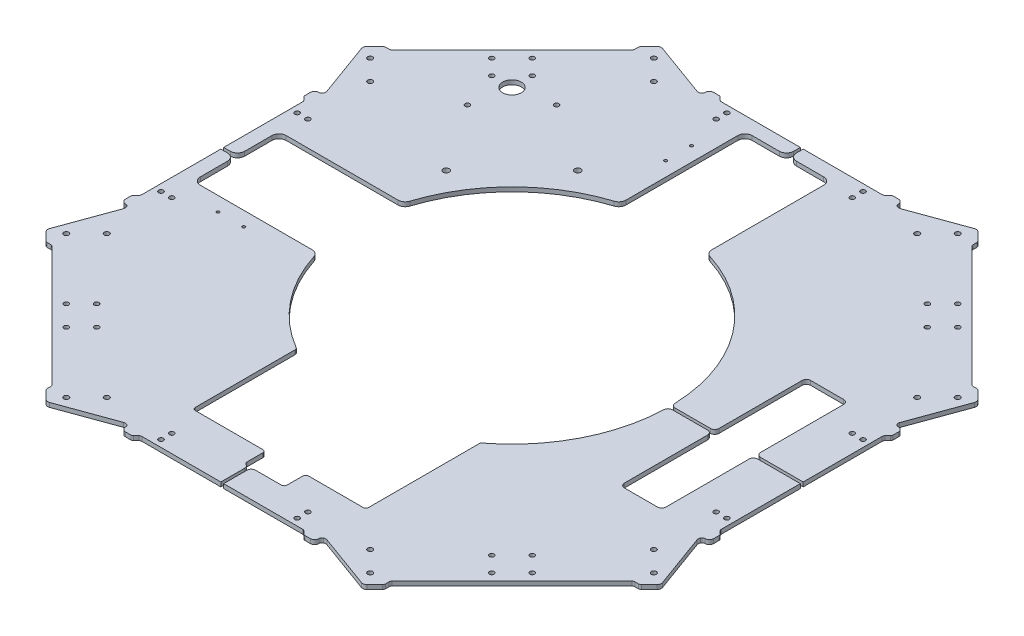
SolidWorks part; units mm, degrees
material "POM 乙缩醛共聚物"
ref_plane "前视基准面" through (0, 0, 0) normal (0, 0, 1) x (1, 0, 0)
ref_plane "上视基准面" through (0, 0, 0) normal (0, 1, 0) x (1, 0, 0)
ref_plane "右视基准面" through (0, 0, 0) normal (1, 0, 0) x (0, 0, -1)
sketch "草图1" plane through (0, 0, 0) normal (0, 1, 0) x (1, 0, 0)
  line L0 (-213.25, 0) -> (213.25, 0) construction
  line L1 (213.25, -47.5) -> (213.25, 47.5) construction
  line L2 (0, -213.25) -> (0, 213.25) construction
  line L3 (-213.25, -47.5) -> (-213.25, 47.5) construction
  line L4 (213.25, 0) -> (221.25, 0) construction
  line L5 (221.25, -67.5) -> (221.25, 67.5)
  line L6 (221.25, 67.5) -> (201.2006, 67.5)
  line L7 (0, 0) -> (180.3122, 180.3122) construction
  line L8 (201.2006, 67.5) -> (67.5, 201.2006)
  line L9 (67.5, 221.25) -> (67.5, 201.2006)
  line L10 (-67.5, 221.25) -> (67.5, 221.25)
  line L11 (-67.5, 221.25) -> (-67.5, 201.2006)
  line L12 (-201.2006, 67.5) -> (-67.5, 201.2006)
  line L13 (-221.25, 67.5) -> (-201.2006, 67.5)
  line L14 (-221.25, -67.5) -> (-221.25, 67.5)
  line L15 (221.25, -67.5) -> (201.2006, -67.5)
  line L16 (201.2006, -67.5) -> (67.5, -201.2006)
  line L17 (67.5, -221.25) -> (67.5, -201.2006)
  line L18 (-221.25, -67.5) -> (-201.2006, -67.5)
  line L19 (-201.2006, -67.5) -> (-67.5, -201.2006)
  line L20 (-67.5, -221.25) -> (-67.5, -201.2006)
  line L21 (-67.5, -221.25) -> (67.5, -221.25)
  circle A0 centre (0, 0) radius 100 construction
  circle A2 centre (0, 0) radius 110
  point P19 (134.3503, 134.3503)
  point P22 (0, 221.25)
  point P31 (-221.25, 0)
  dimension "D1" = 200
  dimension "D4" = 213.25
  dimension "D2" = 213.25
  dimension "D3" = 47.5
  dimension "D5" = 8
  dimension "D6" = 67.5
  dimension "D7" = 10
  dimension "D8" = 255
  dimension "D9" = 65
extrude "凸台-拉伸1" add sketch "草图1" along normal blind 3
sketch "草图2" plane through (0, 3, 0) normal (0, 1, 0) x (1, 0, 0)
  line L0 (0, 0) -> (0, -168) construction
  line L2 (-55, -70) -> (55, -70)
  line L3 (-55, -70) -> (-55, -168)
  line L4 (-55, -168) -> (55, -168)
  line L5 (55, -70) -> (55, -168)
  line L6 (-55, -70) -> (55, -168) construction
  line L7 (-55, -168) -> (55, -70) construction
  point P3 (0, -119)
  dimension "D1" = 168
  dimension "D2" = 110
  dimension "D3" = 98
extrude "切除-拉伸1" cut sketch "草图2" against normal blind 10
sketch "草图3" plane through (0, 3, 0) normal (0, 1, 0) x (1, 0, 0)
  line L0 (55, -168) -> (66, -168)
  line L1 (66, -168) -> (66, -78)
  line L2 (66, -78) -> (55, -78)
  line L3 (55, -78) -> (55, -168)
  dimension "D1" = 11
  dimension "D2" = 90
extrude "切除-拉伸2" cut sketch "草图3" against normal blind 10
sketch "草图4" plane through (0, 3, 0) normal (0, 1, 0) x (1, 0, 0)
  line L0 (-55, -168) -> (66, -168) construction
  line L1 (-4, -153) -> (24, -153)
  line L2 (-4, -153) -> (-4, -183)
  line L3 (-4, -183) -> (24, -183)
  line L4 (24, -153) -> (24, -183)
  line L5 (-4, -153) -> (24, -183) construction
  line L6 (-4, -183) -> (24, -153) construction
  line L7 (0, 0) -> (0, -232.4473) construction
  point P0 (10, -168)
  dimension "D1" = 10
  dimension "D2" = 28
  dimension "D3" = 30
extrude "切除-拉伸3" cut sketch "草图4" against normal blind 10
fillet "圆角1" radius 2 24 edges at (-4, 1.5, 183) (-4, 1.5, 168) (-55, 1.5, 168) (-55, 1.5, 95.2628) (66, 1.5, 88) (66, 1.5, 168) (24, 1.5, 183) (201.2006, 1.5, -67.5) (67.5, 1.5, -201.2006) (67.5, 1.5, -221.25) (-67.5, 1.5, -221.25) (-67.5, 1.5, -201.2006) (-201.2006, 1.5, -67.5) (-221.25, 1.5, -67.5) (-221.25, 1.5, 67.5) (-201.2006, 1.5, 67.5) (-67.5, 1.5, 201.2006) (-67.5, 1.5, 221.25) (67.5, 1.5, 221.25) (67.5, 1.5, 201.2006) (201.2006, 1.5, 67.5) (221.25, 1.5, 67.5) (221.25, 1.5, -67.5) (24, 1.5, 168)
sketch "草图5" plane through (0, 3, 0) normal (0, 1, 0) x (1, 0, 0)
  line L0 (0, 0) -> (-208.25, 0) construction
  line L1 (-208.25, -47.5) -> (-208.25, 47.5) construction
  line L2 (-208.25, 47.5) -> (-197.5, 47.5) construction
  line L3 (-197.5, 47.5) -> (-190, 47.5) construction
  line L4 (-197.5, -47.5) -> (-190, -47.5) construction
  line L5 (-208.25, -47.5) -> (-197.5, -47.5) construction
  line L6 (-47.5, 208.25) -> (47.5, 208.25) construction
  line L7 (0, 208.25) -> (0, 0) construction
  circle A0 centre (-208.25, 47.5) radius 2.65
  circle A1 centre (-197.5, 47.5) radius 1.65
  circle A2 centre (-190, 47.5) radius 1.65
  circle A3 centre (-190, -47.5) radius 1.65
  circle A4 centre (-197.5, -47.5) radius 1.65
  circle A5 centre (-208.25, -47.5) radius 2.65
  circle A24 centre (47.5, 190) radius 1.65
  circle A25 centre (47.5, 197.5) radius 1.65
  circle A26 centre (47.5, 208.25) radius 2.65
  circle A27 centre (-47.5, 208.25) radius 2.65
  circle A28 centre (-47.5, 197.5) radius 1.65
  circle A29 centre (-47.5, 190) radius 1.65
  circle A30 centre (190, -47.5) radius 1.65
  circle A31 centre (197.5, -47.5) radius 1.65
  circle A32 centre (208.25, -47.5) radius 2.65
  circle A33 centre (208.25, 47.5) radius 2.65
  circle A34 centre (197.5, 47.5) radius 1.65
  circle A35 centre (190, 47.5) radius 1.65
  circle A36 centre (-47.5, -190) radius 1.65
  circle A37 centre (-47.5, -197.5) radius 1.65
  circle A38 centre (-47.5, -208.25) radius 2.65
  circle A39 centre (47.5, -208.25) radius 2.65
  circle A40 centre (47.5, -197.5) radius 1.65
  circle A41 centre (47.5, -190) radius 1.65
  point P55 (1.5152, 1.5152)
  dimension "D2" = 5.3
  dimension "D4" = 7.5
  dimension "D5" = 3.3
  dimension "D7" = 95
  dimension "D1" = 208.25
  dimension "D3" = 10.75
  dimension "D6" = 4
extrude "切除-拉伸4" cut sketch "草图5" against normal blind 10
sketch "草图6" plane through (0, 3, 0) normal (0, 1, 0) x (1, 0, 0)
  line L0 (0, 0) -> (0, -221.25) construction
  line L1 (-65.5, -221.25) -> (65.5, -221.25) construction
  line L2 (67.5, -219.25) -> (67.5, -202.029) construction
  line L3 (-67.5, -237.25) -> (67.5, -237.25)
  line L4 (-67.5, -237.25) -> (-67.5, -205.25)
  line L5 (-67.5, -205.25) -> (67.5, -205.25)
  line L6 (67.5, -237.25) -> (67.5, -205.25)
  line L7 (-67.5, -237.25) -> (67.5, -205.25) construction
  line L8 (-67.5, -205.25) -> (67.5, -237.25) construction
  line L9 (-237.25, 67.5) -> (-237.25, -67.5)
  line L10 (-237.25, 67.5) -> (-205.25, 67.5)
  line L11 (-237.25, -67.5) -> (-205.25, -67.5)
  line L12 (-205.25, 67.5) -> (-205.25, -67.5)
  line L21 (-237.25, 67.5) -> (-205.25, -67.5) construction
  line L23 (67.5, 237.25) -> (-67.5, 237.25) [skipped]
  line L24 (67.5, 237.25) -> (67.5, 205.25) [skipped]
  line L25 (-67.5, 237.25) -> (-67.5, 205.25) [skipped]
  line L26 (67.5, 205.25) -> (-67.5, 205.25) [skipped]
  line L27 (237.25, -67.5) -> (237.25, 67.5) [skipped]
  line L28 (237.25, -67.5) -> (205.25, -67.5) [skipped]
  line L29 (237.25, 67.5) -> (205.25, 67.5) [skipped]
  line L30 (205.25, -67.5) -> (205.25, 67.5) [skipped]
  line L34 (237.25, 67.5) -> (205.25, 67.5)
  line L35 (205.25, 67.5) -> (205.25, -67.5)
  line L36 (237.25, -67.5) -> (205.25, -67.5)
  line L37 (237.25, 67.5) -> (237.25, -67.5)
  line L38 (-221.25, 0) -> (0, 0) construction
  line L39 (-219.5626, -92.2876) -> (-219.5626, -92.9346) construction
  line L40 (-67.5, 205.25) -> (67.5, 205.25)
  line L41 (-205.25, 67.5) -> (-237.25, -67.5) construction
  line L42 (67.5, 237.25) -> (67.5, 205.25)
  line L43 (-67.5, 237.25) -> (67.5, 237.25)
  line L44 (-67.5, 237.25) -> (-67.5, 205.25)
  point P26 (0, 0)
  dimension "D1" = 16
  dimension "D2" = 4
extrude "切除-拉伸5" cut sketch "草图6" against normal through all
sketch "草图7" plane through (0, 3, 0) normal (0, 1, 0) x (1, 0, 0)
  line L0 (0, 0) -> (169.5, 0) construction
  line L3 (140.5, 65) -> (169.5, 65)
  line L4 (140.5, 65) -> (140.5, -65)
  line L5 (140.5, -65) -> (169.5, -65)
  line L6 (169.5, 65) -> (169.5, -65)
  line L7 (140.5, 65) -> (169.5, -65) construction
  line L8 (140.5, -65) -> (169.5, 65) construction
  point P5 (155, 0)
  dimension "D1" = 130
  dimension "D2" = 29
  dimension "D3" = 155
extrude "切除-拉伸6" cut sketch "草图7" against normal blind 10
sketch "草图8" plane through (0, 3, 0) normal (0, 1, 0) x (1, 0, 0)
  line L0 (0, 0) -> (134.3503, -134.3503) construction
  line L1 (68.0858, -200.6148) -> (200.6148, -68.0858) construction
  line L2 (134.3503, -134.3503) -> (162.6346, -162.6346) construction
  line L3 (110.6622, -214.6069) -> (214.6069, -110.6622)
  line L4 (214.6069, -110.6622) -> (199.5118, -69.1888)
  line L5 (110.6622, -214.6069) -> (69.1888, -199.5118)
  line L6 (199.5118, -69.1888) -> (69.1888, -199.5118)
  line L7 (0, 0) -> (252.2182, 0) construction
  line L8 (0, 0) -> (0, -92.3729) construction
  line L9 (214.6069, 110.6622) -> (199.5118, 69.1888)
  line L10 (110.6622, 214.6069) -> (214.6069, 110.6622)
  line L11 (110.6622, 214.6069) -> (69.1888, 199.5118)
  line L12 (199.5118, 69.1888) -> (69.1888, 199.5118)
  line L13 (-214.6069, -110.6622) -> (-199.5118, -69.1888)
  line L14 (-110.6622, -214.6069) -> (-214.6069, -110.6622)
  line L15 (-110.6622, -214.6069) -> (-69.1888, -199.5118)
  line L16 (-199.5118, -69.1888) -> (-69.1888, -199.5118)
  line L17 (-110.6622, 214.6069) -> (-214.6069, 110.6622)
  line L18 (-110.6622, 214.6069) -> (-69.1888, 199.5118)
  line L19 (-199.5118, 69.1888) -> (-69.1888, 199.5118)
  line L20 (-214.6069, 110.6622) -> (-199.5118, 69.1888)
  dimension "D1" = 40
  dimension "D2" = 73.5
  dimension "D3" = 115
extrude "凸台-拉伸2" add sketch "草图8" against normal up to surface (3 mm away) up to face at (155, 0, 0)
ref_plane "基准面1" through (0, 0, 0) normal (-0.7071, 0, 0.7071) x (0.7071, 0, 0.7071)
sketch "草图12" plane through (0, 3, 0) normal (0, 1, 0) x (1, 0, 0)
  line L0 (0, 0) -> (162.6346, -162.6346) construction
  line L1 (110.6622, -214.6069) -> (214.6069, -110.6622) construction
  line L2 (155.5635, -155.5635) -> (162.6346, -148.4924) construction
  line L3 (162.6346, -148.4924) -> (152.028, -137.8858) construction
  line L4 (0, 0) -> (24.1105, 24.1105) construction
  line L5 (0, 0) -> (252.2182, 0) construction
  line L6 (162.6346, 148.4924) -> (152.028, 137.8858) construction
  line L7 (252.2182, -23.8295) -> (253.2892, -23.8295) construction
  line L8 (0, 0) -> (0, 85.4115) construction
  line L9 (155.5635, 155.5635) -> (162.6346, 148.4924) construction
  line L10 (-162.6346, -148.4924) -> (-152.028, -137.8858) construction
  line L11 (-155.5635, -155.5635) -> (-162.6346, -148.4924) construction
  line L12 (0, 0) -> (-162.6346, -162.6346) construction
  line L13 (-155.5635, 155.5635) -> (-162.6346, 148.4924) construction
  line L14 (-162.6346, 148.4924) -> (-152.028, 137.8858) construction
  circle A0 centre (162.6346, -148.4924) radius 1.65
  circle A1 centre (152.028, -137.8858) radius 1.65
  circle A2 centre (137.8858, -152.028) radius 1.65
  circle A3 centre (148.4924, -162.6346) radius 1.65
  circle A4 centre (148.4924, 162.6346) radius 1.65
  circle A5 centre (137.8858, 152.028) radius 1.65
  circle A6 centre (152.028, 137.8858) radius 1.65
  circle A7 centre (162.6346, 148.4924) radius 1.65
  circle A8 centre (-148.4924, -162.6346) radius 1.65
  circle A9 centre (-137.8858, -152.028) radius 1.65
  circle A10 centre (-152.028, -137.8858) radius 1.65
  circle A11 centre (-162.6346, -148.4924) radius 1.65
  circle A12 centre (-162.6346, 148.4924) radius 1.65
  circle A13 centre (-152.028, 137.8858) radius 1.65
  circle A14 centre (-137.8858, 152.028) radius 1.65
  circle A15 centre (-148.4924, 162.6346) radius 1.65
  dimension "D1" = 3.3
  dimension "D2" = 3.3
  dimension "D3" = 15
  dimension "D4" = 20
  dimension "D5" = 205
extrude "切除-拉伸7" cut sketch "草图12" against normal blind 112
sketch "草图13" plane through (0, 3, 0) normal (0, 1, 0) x (1, 0, 0)
  line L0 (-205.25, 0) -> (205.25, 0)
  line L1 (-205.25, -67.5) -> (-205.25, 67.5) construction
  line L2 (205.25, 67.5) -> (205.25, -67.5) construction
extrude "切除-拉伸-薄壁1" cut sketch "草图13" against normal through all both and the other way through all thin thin type mid plane wall 2
sketch "草图14" plane through (0, 3, 0) normal (0, 1, 0) x (1, 0, 0)
  line L0 (0, 205.25) -> (0, -205.25)
  line L1 (-67.5, 205.25) -> (67.5, 205.25) construction
  line L2 (67.5, -205.25) -> (-67.5, -205.25) construction
extrude "切除-拉伸-薄壁2" cut sketch "草图14" against normal through all and the other way through all thin thin type mid plane wall 2
fillet "圆角2" radius 3 8 edges at (-1, 1.5, 205.25) (-69.1888, 1.5, 199.5118) (-67.5, 1.5, 205.25) (-205.25, 1.5, 1) (-199.5118, 1.5, 69.1888) (-205.25, 1.5, 67.5) (-214.6069, 1.5, 110.6622) (-110.6622, 1.5, 214.6069)
fillet "圆角3" radius 3 14 edges at (169.5, 1.5, 65) (140.5, 1.5, 65) (109.9955, 1.5, 1) (140.5, 1.5, 1) (169.5, 1.5, 1) (205.25, 1.5, 1) (205.25, 1.5, 67.5) (199.5118, 1.5, 69.1888) (214.6069, 1.5, 110.6622) (110.6622, 1.5, 214.6069) (69.1888, 1.5, 199.5118) (67.5, 1.5, 205.25) (1, 1.5, 183) (1, 1.5, 205.25)
fillet "圆角4" radius 3 13 edges at (1, 1.5, -109.9955) (1, 1.5, -205.25) (69.1888, 1.5, -199.5118) (67.5, 1.5, -205.25) (110.6622, 1.5, -214.6069) (214.6069, 1.5, -110.6622) (205.25, 1.5, -67.5) (169.5, 1.5, -65) (140.5, 1.5, -65) (109.9955, 1.5, -1) (140.5, 1.5, -1) (169.5, 1.5, -1) (205.25, 1.5, -1)
fillet "圆角5" radius 3 10 edges at (-67.5, 1.5, -205.25) (-69.1888, 1.5, -199.5118) (-110.6622, 1.5, -214.6069) (-214.6069, 1.5, -110.6622) (-199.5118, 1.5, -69.1888) (-205.25, 1.5, -67.5) (-205.25, 1.5, -1) (-109.9955, 1.5, -1) (-1, 1.5, -109.9955) (-1, 1.5, -205.25)
fillet "圆角6" radius 3 2 edges at (-1, 1.5, 183) (-109.9955, 1.5, 1)
sketch "草图15" plane through (0, 0, 0) normal (0, -1, 0) x (1, 0, 0)
  line L0 (148.4924, -162.6346) -> (106.066, -205.061) construction
  line L1 (162.6346, -162.6346) -> (105.0927, -105.0927) construction
  line L2 (112.0136, -213.2555) -> (213.2555, -112.0136) construction
  line L3 (162.6346, -162.6346) -> (213.2555, -112.0136) construction
  line L4 (106.066, -205.061) -> (91.9239, -190.9188) construction
  line L5 (205.061, -106.066) -> (190.9188, -91.9239) construction
  line L6 (162.6346, -148.4924) -> (205.061, -106.066) construction
  line L7 (0, 0) -> (248.6294, 0) construction
  line L8 (0, 0) -> (0, -244.0653) construction
  line L9 (-162.6346, -148.4924) -> (-205.061, -106.066) construction
  line L10 (-205.061, -106.066) -> (-190.9188, -91.9239) construction
  line L11 (-106.066, -205.061) -> (-91.9239, -190.9188) construction
  line L12 (-162.6346, -162.6346) -> (-213.2555, -112.0136) construction
  line L13 (-162.6346, -162.6346) -> (-105.0927, -105.0927) construction
  line L14 (-148.4924, -162.6346) -> (-106.066, -205.061) construction
  line L15 (-148.4924, 162.6346) -> (-106.066, 205.061) construction
  line L16 (-162.6346, 162.6346) -> (-105.0927, 105.0927) construction
  line L17 (-162.6346, 162.6346) -> (-213.2555, 112.0136) construction
  line L18 (-106.066, 205.061) -> (-91.9239, 190.9188) construction
  line L19 (-205.061, 106.066) -> (-190.9188, 91.9239) construction
  line L20 (-162.6346, 148.4924) -> (-205.061, 106.066) construction
  line L21 (162.6346, 148.4924) -> (205.061, 106.066) construction
  line L22 (205.061, 106.066) -> (190.9188, 91.9239) construction
  line L23 (106.066, 205.061) -> (91.9239, 190.9188) construction
  line L24 (162.6346, 162.6346) -> (213.2555, 112.0136) construction
  line L25 (162.6346, 162.6346) -> (105.0927, 105.0927) construction
  line L26 (148.4924, 162.6346) -> (106.066, 205.061) construction
  circle A0 centre (106.066, -205.061) radius 1.75
  circle A1 centre (91.9239, -190.9188) radius 1.75
  circle A2 centre (190.9188, -91.9239) radius 1.75
  circle A3 centre (205.061, -106.066) radius 1.75
  circle A4 centre (-205.061, -106.066) radius 1.75
  circle A5 centre (-190.9188, -91.9239) radius 1.75
  circle A6 centre (-91.9239, -190.9188) radius 1.75
  circle A7 centre (-106.066, -205.061) radius 1.75
  circle A8 centre (-106.066, 205.061) radius 1.75
  circle A9 centre (-91.9239, 190.9188) radius 1.75
  circle A10 centre (-190.9188, 91.9239) radius 1.75
  circle A11 centre (-205.061, 106.066) radius 1.75
  circle A12 centre (205.061, 106.066) radius 1.75
  circle A13 centre (190.9188, 91.9239) radius 1.75
  circle A14 centre (91.9239, 190.9188) radius 1.75
  circle A15 centre (106.066, 205.061) radius 1.75
  dimension "D2" = 3.5
  dimension "D4" = 3.5
  dimension "D1" = 140
  dimension "D3" = 20
extrude "切除-拉伸8" cut sketch "草图15" against normal blind 10
sketch "草图16" plane through (0, 3, 0) normal (0, 1, 0) x (1, 0, 0)
  line L0 (0, 0) -> (-162.6346, 162.6346) construction
  line L1 (-112.0136, 213.2555) -> (-213.2555, 112.0136) construction
  line L2 (-127.2792, 127.2792) -> (-111.7229, 142.8356) construction
  line L3 (-87.6812, 87.6812) -> (-64.7003, 110.6622) construction
  circle A0 centre (-111.7229, 142.8356) radius 1.65
  circle A1 centre (-64.7003, 110.6622) radius 2.15
  circle A2 centre (-110.6622, 64.7003) radius 2.15
  circle A3 centre (-142.8356, 111.7229) radius 1.65
  dimension "D3" = 3.3
  dimension "D4" = 4.3
  dimension "D5" = 65
  dimension "D6" = 56
  dimension "D1" = 22
  dimension "D2" = 180
extrude "切除-拉伸9" cut sketch "草图16" against normal blind 10
sketch "草图17" plane through (0, 0, 0) normal (0, -1, 0) x (1, 0, 0)
  line L0 (0, 0) -> (-162.6346, -162.6346) construction
  line L1 (-213.2555, -112.0136) -> (-112.0136, -213.2555) construction
  circle A0 centre (-137.8858, -137.8858) radius 6.5
  dimension "D1" = 13
  dimension "D2" = 35
extrude "切除-拉伸10" cut sketch "草图17" against normal through all
sketch "草图18" plane through (0, 0, 0) normal (0, -1, 0) x (1, 0, 0)
  line L0 (-1, -157.5896) -> (1, -157.5896) construction
  line L1 (-1, -202.25) -> (-1, -112.9292) construction
  line L2 (1, -202.25) -> (1, -112.9292) construction
  line L3 (0, -157.5896) -> (0, -81.3505) construction
  line L8 (-40, -165.25) -> (-40, -147.25) construction
  line L9 (-30, -102.5896) -> (30, -102.5896)
  line L10 (-30, -102.5896) -> (-30, -192.5896)
  line L11 (-30, -192.5896) -> (30, -192.5896)
  line L12 (30, -102.5896) -> (30, -192.5896)
  line L13 (-30, -102.5896) -> (30, -192.5896) construction
  line L14 (-30, -192.5896) -> (30, -102.5896) construction
  line L16 (-64.5, -205.25) -> (-4, -205.25) construction
  circle A0 centre (-40, -147.25) radius 1
  circle A1 centre (-40, -165.25) radius 1
  point P4 (0, -157.5896)
  point P9 (0, -147.5896)
  dimension "D4" = 2
  dimension "D6" = 40
  dimension "D7" = 40
  dimension "D1" = 10
  dimension "D2" = 90
  dimension "D3" = 60
  dimension "D5" = 18
extrude "切除-拉伸11" cut sketch "草图18" against normal through all
sketch "草图20" plane through (0, 0, 0) normal (0, -1, 0) x (1, 0, 0)
  line L0 (-157.5896, -1) -> (-157.5896, 1) construction
  line L1 (-202.25, -1) -> (-112.9292, -1) construction
  line L2 (-202.25, 1) -> (-112.9292, 1) construction
  line L3 (-157.5896, 0) -> (-106.515, 0) construction
  line L4 (-165.25, 40) -> (-147.25, 40) construction
  line L5 (-192.5896, 30) -> (-102.5896, 30)
  line L6 (-192.5896, 30) -> (-192.5896, -30)
  line L7 (-192.5896, -30) -> (-102.5896, -30)
  line L8 (-102.5896, 30) -> (-102.5896, -30)
  line L9 (-192.5896, 30) -> (-102.5896, -30) construction
  line L10 (-192.5896, -30) -> (-102.5896, 30) construction
  line L11 (-205.25, 64.5) -> (-205.25, 4) construction
  circle A0 centre (-147.25, 40) radius 1
  circle A1 centre (-165.25, 40) radius 1
  point P9 (-147.5896, 0)
  dimension "D4" = 2
  dimension "D5" = 18
  dimension "D1" = 60
  dimension "D2" = 90
  dimension "D3" = 10
  dimension "D6" = 40
  dimension "D7" = 40
extrude "切除-拉伸13" cut sketch "草图20" against normal through all
fillet "圆角7" radius 5 3 edges at (-192.5896, 1.5, 1) (-192.5896, 1.5, 30) (-105.8301, 1.5, 30)
fillet "圆角8" radius 5 6 edges at (-1, 1.5, -192.5896) (-30, 1.5, -192.5896) (-30, 1.5, -105.8301) (-105.8301, 1.5, -30) (-192.5896, 1.5, -30) (-192.5896, 1.5, -1)
fillet "圆角9" radius 5 3 edges at (30, 1.5, -105.8301) (30, 1.5, -192.5896) (1, 1.5, -192.5896)
sketch "草图21" plane through (0, 3, 0) normal (0, 1, 0) x (1, 0, 0)
  line L0 (-162.6346, 162.6346) -> (-139.5333, 139.5333) construction
  line L1 (-112.0136, 213.2555) -> (-213.2555, 112.0136) construction
  line L2 (-118.0868, 207.1823) -> (-207.1823, 118.0868)
  line L4 (-118.0868, 202.9396) -> (-202.9396, 118.0868)
  line L6 (0, 0) -> (-240.1216, 0) construction
  line L7 (0, 0) -> (0, 249.8276) construction
  line L8 (207.1823, 118.0868) -> (202.9396, 118.0868)
  line L9 (118.0868, 207.1823) -> (118.0868, 202.9396)
  line L10 (118.0868, 202.9396) -> (202.9396, 118.0868)
  line L11 (118.0868, 207.1823) -> (207.1823, 118.0868)
  line L12 (-207.1823, -118.0868) -> (-118.0868, -207.1823)
  line L13 (-202.9396, -118.0868) -> (-118.0868, -202.9396)
  line L14 (-207.1823, -118.0868) -> (-202.9396, -118.0868)
  line L15 (-118.0868, -207.1823) -> (-118.0868, -202.9396)
  line L16 (-118.0868, 207.1823) -> (-118.0868, 202.9396)
  line L18 (118.0868, -207.1823) -> (207.1823, -118.0868)
  line L19 (118.0868, -202.9396) -> (202.9396, -118.0868)
  line L20 (118.0868, -207.1823) -> (118.0868, -202.9396)
  line L21 (207.1823, -118.0868) -> (202.9396, -118.0868)
  line L22 (-202.9396, 118.0868) -> (-207.1823, 118.0868)
  point P9 (-160.5132, 160.5132)
  line M16 (-112.0136, 213.2555) -> (-213.2555, 112.0136)
  dimension "D1" = 60
  dimension "D2" = 3
extrude "切除-拉伸15" cut sketch "草图21" against normal blind 10 contours L18 L21 L19 L20 | L12 L15 L13 L14 | L11 L9 L10 L8 | L22 L4 L16 M16
fillet "圆角12" radius 2 4 edges at (-118.0868, 1.5, -207.1823) (-118.0868, 1.5, -202.9396) (-207.1823, 1.5, -118.0868) (-202.9396, 1.5, -118.0868)
fillet "圆角13" radius 2 4 edges at (-118.0868, 1.5, 207.1823) (-118.0868, 1.5, 202.9396) (-202.9396, 1.5, 118.0868) (-207.1823, 1.5, 118.0868)
fillet "圆角14" radius 2 4 edges at (202.9396, 1.5, 118.0868) (207.1823, 1.5, 118.0868) (118.0868, 1.5, 207.1823) (118.0868, 1.5, 202.9396)
fillet "圆角15" radius 2 4 edges at (207.1823, 1.5, -118.0868) (202.9396, 1.5, -118.0868) (118.0868, 1.5, -207.1823) (118.0868, 1.5, -202.9396)
sketch "草图23" plane through (0, 3, 0) normal (0, 1, 0) x (1, 0, 0)
  line L0 (0, 0) -> (0, -337.8047) construction
  line L1 (-60, -205.25) -> (-57, -202.25)
  line L2 (-4, -205.25) -> (-64.5, -205.25) construction
  line L3 (-57, -202.25) -> (57, -202.25)
  line L4 (60, -205.25) -> (-60, -205.25)
  line L5 (60, -205.25) -> (57, -202.25)
  line L6 (0, 0) -> (160.5132, -160.5132) construction
  line L7 (118.6726, -202.3539) -> (202.3539, -118.6726) construction
  line L8 (205.25, -60) -> (202.25, -57)
  line L9 (205.25, -60) -> (205.25, 60)
  line L10 (202.25, 57) -> (202.25, -57)
  line L11 (205.25, 60) -> (202.25, 57)
  line L12 (0, 0) -> (-251.092, 0) construction
  line L13 (60, 205.25) -> (57, 202.25)
  line L14 (60, 205.25) -> (-60, 205.25)
  line L15 (-57, 202.25) -> (57, 202.25)
  line L16 (-60, 205.25) -> (-57, 202.25)
  line L17 (-205.25, 60) -> (-202.25, 57)
  line L18 (-202.25, 57) -> (-202.25, -57)
  line L19 (-205.25, -60) -> (-205.25, 60)
  line L20 (-205.25, -60) -> (-202.25, -57)
  point P11 (0, -205.25)
  point P12 (0, -202.25)
  point P18 (202.25, 0)
  point P19 (205.25, 0)
  point P25 (0, 202.25)
  point P26 (0, 205.25)
  point P31 (-205.25, 0)
  point P32 (-202.25, 0)
  dimension "D1" = 135
  dimension "D2" = 60
  dimension "D3" = 3
extrude "切除-拉伸17" cut sketch "草图23" against normal blind 10
fillet "圆角16" radius 2 6 edges at (-205.25, 1.5, 60) (-202.25, 1.5, 57) (-200.6148, 1.5, 68.0858) (-68.0858, 1.5, 200.6148) (-60, 1.5, 205.25) (-57, 1.5, 202.25)
fillet "圆角17" radius 2 6 edges at (-68.0858, 1.5, -200.6148) (-60, 1.5, -205.25) (-57, 1.5, -202.25) (-200.6148, 1.5, -68.0858) (-205.25, 1.5, -60) (-202.25, 1.5, -57)
fillet "圆角18" radius 2 6 edges at (68.0858, 1.5, -200.6148) (60, 1.5, -205.25) (57, 1.5, -202.25) (199.5118, 1.5, -69.1888) (205.25, 1.5, -60) (202.25, 1.5, -57)
fillet "圆角19" radius 2 6 edges at (68.0858, 1.5, 200.6148) (57, 1.5, 202.25) (60, 1.5, 205.25) (200.6148, 1.5, 68.0858) (205.25, 1.5, 60) (202.25, 1.5, 57)
